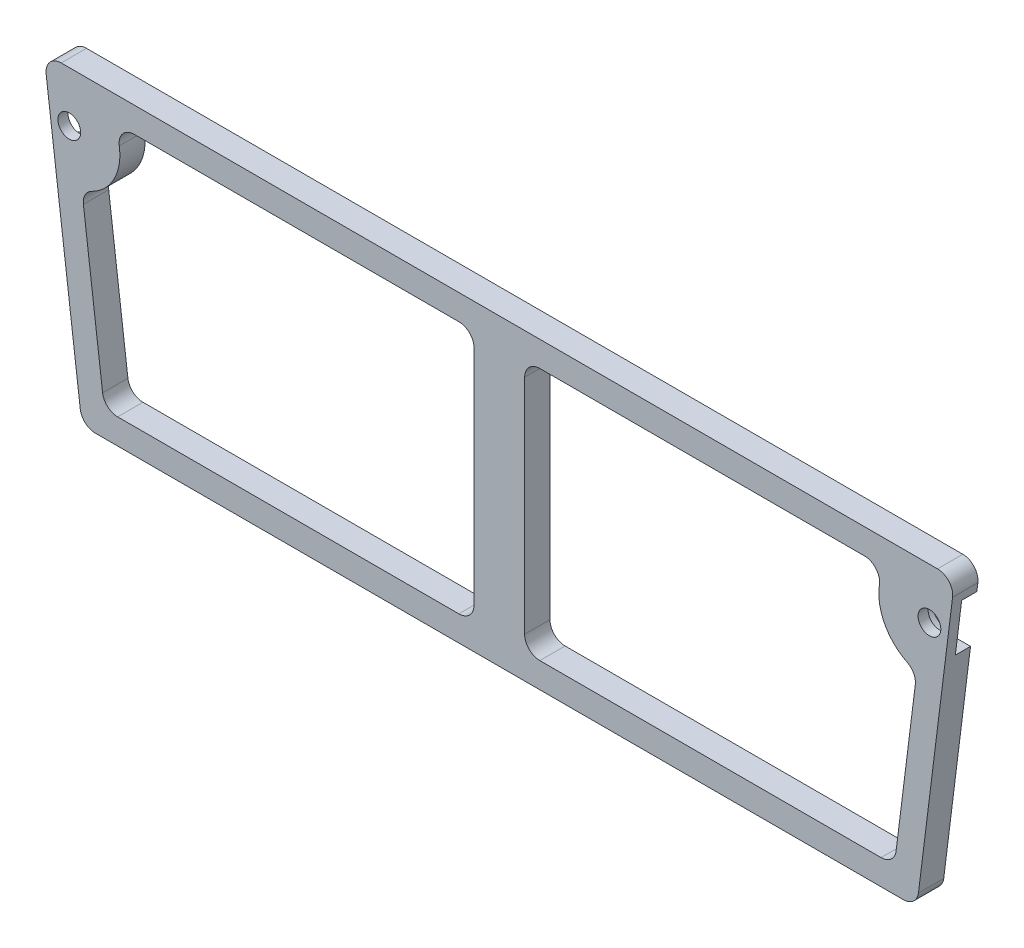
SolidWorks part; units mm, degrees
ref_plane "Płaszczyzna przednia" through (0, 0, 0) normal (0, 0, 1) x (1, 0, 0)
ref_plane "Płaszczyzna górna" through (0, 0, 0) normal (0, 1, 0) x (1, 0, 0)
ref_plane "Płaszczyzna prawa" through (0, 0, 0) normal (1, 0, 0) x (0, 0, -1)
sketch "Szkic1" plane through (0, 0, 0) normal (0, 0, 1) x (1, 0, 0)
  line L0 (-90, 0) -> (0, 0)
  line L2 (0, -60) -> (-82.5, -60)
  line L3 (-82.5, -60) -> (-90, 0)
  line L4 (0, 0) -> (0, -60)
  line L5 (-85, -5) -> (-90, -5)
  line L6 (-85, -5) -> (-85, -15)
  line L7 (-85, -15) -> (-90, -15)
  line L8 (-90, -5) -> (-90, -15)
  circle A1 centre (-85, -10) radius 5
  circle A2 centre (-85, -10) radius 2.25
  dimension "D6" = 10
  dimension "D7" = 4.5
  dimension "D1" = 90
  dimension "D2" = 60
  dimension "D3" = 82.5
  dimension "D4" = 5
  dimension "D5" = 10
  dimension "D8" = 10
extrude "Dodanie-wyciągnięcie1" add sketch "Szkic1" along normal blind 5 contours A1 L7 L3 L2 L4 L0 L5 | A1 L5 L3 | A2 L6 A1 | A2 L6 A1 L3 | A1 L3 L7 region at (-42.5244, -29.8619, 0) region at (-88.2346, -5.6212, 0) region at (-87.267, -5.6651, 0) region at (-82.5816, -10, 0) region at (-87.4202, -14.6459, 0)
extrude "Wytnij-wyciągnięcie1" cut sketch "Szkic1<3>" along normal blind 3 contours A2 L6 A1 | A2 L6 A1 L3 | A1 L5 L3 | A1 L3 L7 | A1 region at (-88.2346, -5.6212, 0) region at (-87.267, -5.6651, 0) region at (-82.5816, -10, 0) region at (-87.4202, -14.6459, 0)
sketch "Szkic1<3>" plane through (0, 0, 0) normal (0, 0, 1) x (1, 0, 0) same geometry as "Szkic1"
ref_plane "Płaszczyzna1" through (0, 0, 0) normal (1, 0, 0) x (0, 0, -1)
fillet "Zaokrąglenie3" radius 3 2 edges at (-82.5, -60, 2.5) (-90, 0, 2.5)
sketch "Szkic5" plane through (0, 0, 0) normal (0, 0, -1) x (-1, 0, 0)
  line L0 (5, -55) -> (78.0861, -55)
  line L1 (78.0861, -55) -> (82.5008, -19.6827)
  line L2 (82.5008, -19.6827) -> (82.5008, -19.6827)
  line L3 (76.3397, -5) -> (76.3397, -5)
  line L4 (76.3397, -5) -> (76.3397, -5)
  line L5 (76.3397, -5) -> (5, -5)
  line L6 (5, -5) -> (5, -55)
  line L7 (0, -60) -> (79.8517, -60)
  line L8 (82.8285, -57.3721) -> (88.125, -15)
  line L9 (88.125, -15) -> (85, -15)
  line L10 (85, -5) -> (89.375, -5)
  line L11 (89.375, -5) -> (89.5785, -3.3721)
  line L12 (86.6017, 0) -> (0, 0)
  line L13 (0, 0) -> (0, -60)
  line L14 (0, -60) -> (79.8517, -60)
  line L15 (82.8285, -57.3721) -> (88.125, -15)
  line L16 (88.125, -15) -> (85, -15)
  line L17 (85, -5) -> (89.375, -5)
  line L18 (89.375, -5) -> (89.5785, -3.3721)
  line L19 (86.6017, 0) -> (0, 0)
  line L20 (0, 0) -> (0, -60)
  arc A0 (78.0861, -55) -> (78.0861, -55) centre (78.0861, -55) ccw
  arc A1 (76.3397, -5) -> (82.5008, -19.6827) centre (85, -10) ccw
  arc A2 (76.3397, -5) -> (76.3397, -5) centre (76.3397, -5) ccw
  arc A3 (79.8517, -60) -> (82.8285, -57.3721) centre (79.8517, -57) ccw
  arc A4 (85, -5) -> (85, -15) centre (85, -10) ccw
  arc A5 (89.5785, -3.3721) -> (86.6017, 0) centre (86.6017, -3) ccw
  arc A6 (79.8517, -60) -> (82.8285, -57.3721) centre (79.8517, -57) ccw
  arc A7 (85, -5) -> (85, -15) centre (85, -10) ccw
  arc A8 (89.5785, -3.3721) -> (86.6017, 0) centre (86.6017, -3) ccw
  dimension "D1" = 0
  dimension "D2" = 5
extrude "Wytnij-wyciągnięcie3" cut sketch "Szkic5" against normal through all contours A1 L2 L1 A0 L0 L6 L5 A2 L4 L3
fillet "Zaokrąglenie4" radius 3 5 edges at (-5, -5, 2.5) (-5, -55, 2.5) (-78.0861, -55, 2.5) (-82.5008, -19.6827, 2.5) (-76.3397, -5, 2.5)
mirror "Lustro5" about plane through (0, 0, 0) normal (1, 0, 0) of bodies 105
